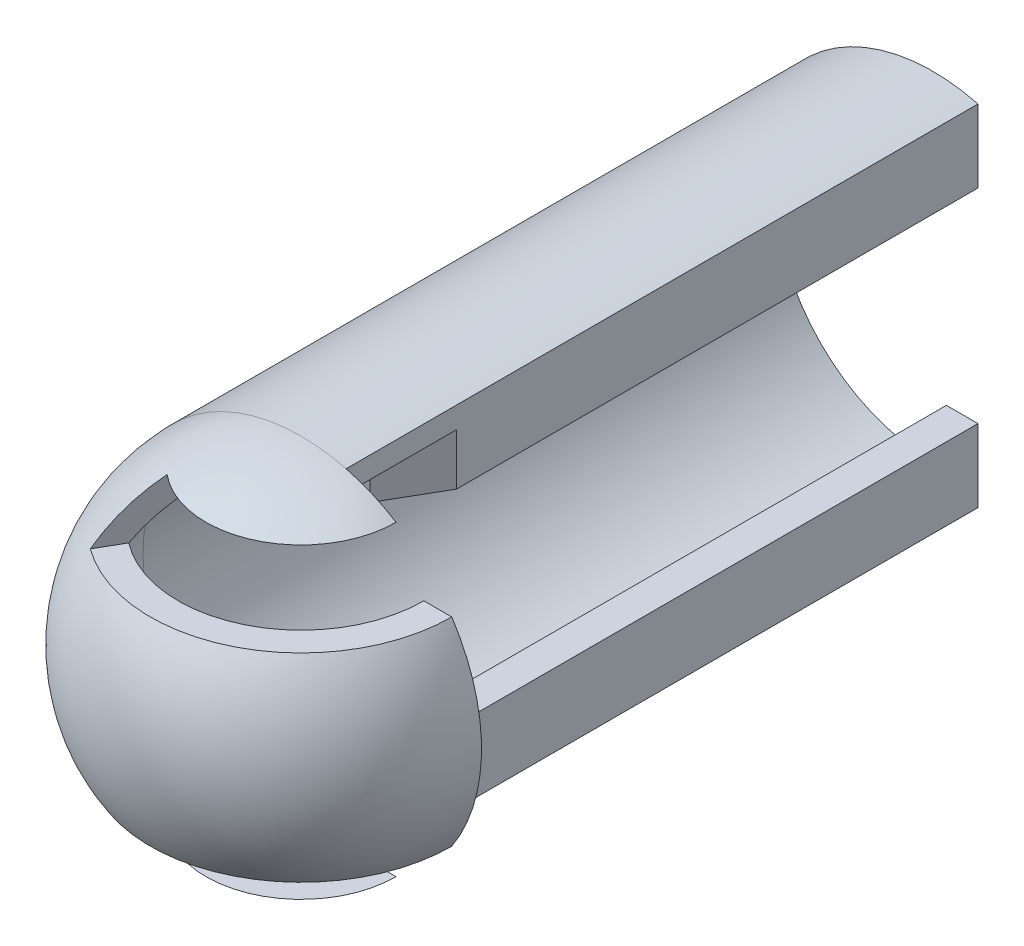
SolidWorks part; units mm, degrees
ref_plane "Front Plane" through (0, 0, 0) normal (0, 0, 1) x (1, 0, 0)
ref_plane "Top Plane" through (0, 0, 0) normal (0, 1, 0) x (1, 0, 0)
ref_plane "Right Plane" through (0, 0, 0) normal (1, 0, 0) x (0, 0, -1)
sketch "Sketch1" plane through (0, 0, 0) normal (0, 0, 1) x (1, 0, 0)
  line L3 (10, 38.7298) -> (10, 22.6)
  line L4 (10, 22.6) -> (3, 22.6)
  line L5 (3, 22.6) -> (3, 34.8712)
  line L6 (10, 0) -> (-40, 0) construction
  line L7 (10, -38.7298) -> (10, -22.6)
  line L8 (10, -22.6) -> (3, -22.6)
  line L9 (3, -22.6) -> (3, -34.8712)
  arc A0 (10, 38.7298) -> (10, -38.7298) centre (0, 0) ccw
  arc A2 (3, 34.8712) -> (3, -34.8712) centre (0, 0) ccw
  circle A4 centre (0, 0) radius 40 construction
  circle A5 centre (0, 0) radius 35 construction
  point P1 (14.995, 13.5)
  point P9 (18.4657, 23.733)
  dimension "D1" = 80
  dimension "D3" = 10
  dimension "D4" = 45.2
  dimension "D5" = 3
  dimension "D2" = 5
extrude "Boss-Extrude1" add sketch "Sketch1" against normal blind 140
ref_plane "Plane1" through (0, 40, 0) normal (0, 1, 0) x (1, 0, 0)
sketch "Sketch6" plane through (0, 0, 0) normal (0, 0, 1) x (1, 0, 0)
  line L0 (0, 40) -> (0, 35)
  line L1 (0, -40) -> (0, -35)
  line L2 (0, 40) -> (0, -40) construction
  line L4 (3, 34.8712) -> (3, 22.6)
  line L5 (3, 34.8712) -> (3, 22.6)
  line L11 (3, 22.6) -> (10, 22.6)
  line L12 (3, 22.6) -> (10, 22.6)
  line L13 (10, 22.6) -> (10, 38.7298)
  line L14 (10, 22.6) -> (10, 38.7298)
  line L15 (10, -38.7298) -> (10, -22.6)
  line L16 (10, -38.7298) -> (10, -22.6)
  line L17 (10, -22.6) -> (3, -22.6)
  line L18 (10, -22.6) -> (3, -22.6)
  line L19 (3, -22.6) -> (3, -34.8712)
  line L20 (3, -22.6) -> (3, -34.8712)
  arc A4 (10, 38.7298) -> (10, -38.7298) centre (0, 0) ccw
  arc A5 (3, 34.8712) -> (3, -34.8712) centre (0, 0) ccw
  arc A6 (10, 38.7298) -> (10, -38.7298) centre (0, 0) ccw
  arc A7 (3, 34.8712) -> (3, -34.8712) centre (0, 0) ccw
  point P6 (-40, 0)
  dimension "D2" = 40
  dimension "D1" = 0
revolve "Revolve1" add sketch "Sketch6" angle 180 about L2 region at (-0.8944, 37.5, 0) reverse direction yes
sketch "Sketch2" plane through (0, 40, 0) normal (0, 1, 0) x (1, 0, 0)
  line L0 (16.8315, 36.2864) -> (-23.0092, -32.7197)
  line L1 (10, 140) -> (10, 0) construction
  line L2 (10, 24.4538) -> (10, -38.7298) construction
  line L3 (15.8082, 0) -> (-1.2349, 0) construction
  arc A0 (1.5685, 9.85) -> (-1.2349, 0) centre (19.755, -0.65) ccw construction
  arc A2 (-23.0092, -32.7197) -> (16.8315, 36.2864) centre (0, 0) ccw
  arc A3 (-40, 0) -> (40, 0) centre (0, 0) ccw construction
  circle A4 centre (19.755, -0.65) radius 4 construction
  arc A5 (20.5277, 19.3351) -> (18.9823, -20.6351) centre (19.755, -0.65) ccw construction
  point P2 (15.005, -0.65)
  point P8 (9.8884, 32.4878)
  point P19 (12.9765, 37.7337)
  point P20 (0, 0)
  dimension "D1" = 1
  dimension "D2" = 30
extrude "Cut-Extrude1" cut sketch "Sketch2" against normal blind 12 from offset 6 contours L0 A2 L2 region at (13.0478, 40, 7.5331) offset against normal yes
ref_plane "Plane2" [suppressed] through (0, 0, 0) normal (0, 0, -1) x (-1, 0, 0)
sketch "Sketch7" [suppressed] plane through (0, 0, 0) normal (0, 0, -1) x (-1, 0, 0)
  line L0 (5.9849, 39.5497) -> (-2, 39.5497)
  line L3 (-2, 34.4845) -> (-2, -34.4845) construction
  line L6 (-2, -40) -> (-2, 39.5497)
  line L7 (5.9849, -40) -> (-2, -40)
  line L8 (5.9849, 39.5497) -> (5.9849, -40)
  arc A0 (-10, -38.7298) -> (-10, 38.7298) centre (0, 0) ccw construction
extrude "Cut-Extrude2" [suppressed] cut sketch "Sketch7" against normal through all
mirror "Mirror1" about plane through (0, 0, 0) normal (0, 1, 0) of "Cut-Extrude1"
